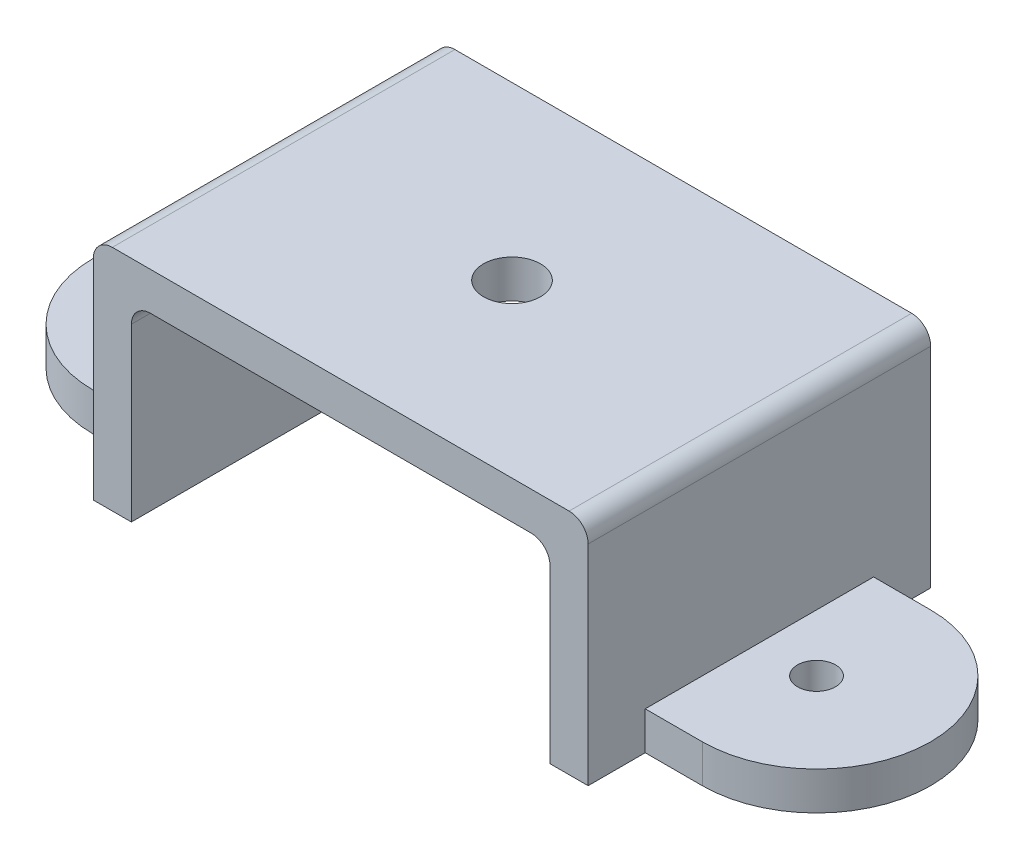
SolidWorks part; units mm, degrees
ref_plane "Front Plane" through (0, 0, 0) normal (0, 0, 1) x (1, 0, 0)
ref_plane "Top Plane" through (0, 0, 0) normal (0, 1, 0) x (1, 0, 0)
ref_plane "Right Plane" through (0, 0, 0) normal (1, 0, 0) x (0, 0, -1)
sketch "Sketch1" plane through (0, 0, 0) normal (0, 1, 0) x (1, 0, 0)
  line L1 (-101.6, 38.1) -> (101.6, 38.1)
  line L2 (-101.6, 38.1) -> (-101.6, -38.1)
  line L3 (-101.6, -38.1) -> (101.6, -38.1)
  line L4 (101.6, 38.1) -> (101.6, -38.1)
  circle A0 centre (-101.6, 0) radius 38.1
  circle A1 centre (101.6, 0) radius 38.1
  dimension "D1" = 76.2
  dimension "D2" = 203.2
  dimension "D3" = 101.6
  dimension "D4" = 38.1
extrude "Boss-Extrude1" add sketch "Sketch1" along normal blind 12.7 contours A1 L1 A0 L3 | L2 A0 | L2 A0 | L4 A1 | L4 A1 region at (-85.4299, 0, 0) region at (0, 0, 0) region at (-117.7701, 0, 0) region at (117.7701, 0, 0) region at (85.4299, 0, 0)
sketch "Sketch2" plane through (0, 0, 0) normal (0, 0, 1) x (1, 0, 0)
  line L0 (-101.6, 0) -> (101.6, 0) construction
  line L1 (-82.55, 0) -> (-69.85, 0)
  line L2 (69.85, 0) -> (82.55, 0)
  line L4 (-82.55, 0) -> (82.55, 0)
  line L5 (-82.55, 0) -> (-82.55, 76.2)
  line L6 (-82.55, 76.2) -> (82.55, 76.2)
  line L7 (82.55, 0) -> (82.55, 76.2)
  line L8 (-69.85, 0) -> (69.85, 0)
  line L9 (-69.85, 0) -> (-69.85, 63.5)
  line L10 (-69.85, 63.5) -> (69.85, 63.5)
  line L11 (69.85, 0) -> (69.85, 63.5)
  dimension "D1" = 165.1
  dimension "D2" = 139.7
  dimension "D3" = 12.7
  dimension "D4" = 76.2
  dimension "D5" = 12.7
  dimension "D6" = 69.85
extrude "Boss-Extrude2" add sketch "Sketch2" along normal blind 57.15 and the other way blind 57.15 contours L11 L2 L7 L6 L5 L1 L9 L10 region at (-80.7316, 38.1, 0)
sketch "Sketch8" plane through (0, 0, 0) normal (0, 1, 0) x (1, 0, 0)
  circle A0 centre (0, 0) radius 9.525
  dimension "D1" = 19.05
extrude "Cut-Extrude2" cut sketch "Sketch8" along normal through all
sketch "Sketch9" plane through (0, 0, 57.15) normal (0, 0, 1) x (1, 0, 0)
  line L0 (-69.85, 0) -> (69.85, 0)
  line L1 (69.85, 0) -> (69.85, 63.5)
  line L2 (69.85, 63.5) -> (-69.85, 63.5)
  line L3 (-69.85, 63.5) -> (-69.85, 0)
extrude "Cut-Extrude3" cut sketch "Sketch9" against normal through all
fillet "Fillet1" radius 6.35 4 edges at (-69.85, 63.5, 0) (69.85, 63.5, 0) (82.55, 76.2, 0) (-82.55, 76.2, 0)
sketch "Sketch10" plane through (0, 12.7, 0) normal (0, 1, 0) x (1, 0, 0)
  circle A0 centre (101.6, 0) radius 6.35
  circle A1 centre (-101.6, 0) radius 6.35
  arc A2 (-101.6, 38.1) -> (-101.6, -38.1) centre (-101.6, 0) ccw construction
  arc A3 (101.6, -38.1) -> (101.6, 38.1) centre (101.6, 0) ccw construction
  dimension "D1" = 12.7
extrude "Cut-Extrude4" cut sketch "Sketch10" against normal through all
